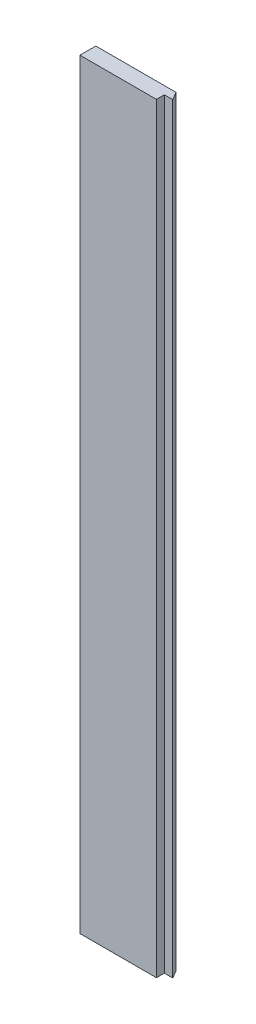
SolidWorks part; units mm, degrees
ref_plane "Front Plane" through (0, 0, 0) normal (0, 0, 1) x (1, 0, 0)
ref_plane "Top Plane" through (0, 0, 0) normal (0, 1, 0) x (1, 0, 0)
ref_plane "Right Plane" through (0, 0, 0) normal (1, 0, 0) x (0, 0, -1)
sketch "Sketch1" plane through (0, 0, 0) normal (0, 1, 0) x (1, 0, 0)
  line L0 (-60, 0) -> (-41.5, 0)
  line L1 (-60, 9) -> (60, 9)
  line L2 (-60, 9) -> (-60, -9)
  line L3 (-60, -9) -> (60, -9)
  line L4 (60, 9) -> (60, -9)
  line L5 (-60, 9) -> (60, -9) construction
  line L6 (-60, -9) -> (60, 9) construction
  line L7 (-41.5, 0) -> (-36.3038, 9)
  line L8 (-41.5, 0) -> (-41.5, 9) construction
  line L9 (60, 0) -> (54.8038, 9)
  line L10 (60, 0) -> (50.5, 0)
  line L11 (50.5, 0) -> (50.5, -9)
  line L13 (0, 9) -> (0, -9) construction
  point P0 (0, 0)
  dimension "D1" = 120
  dimension "D2" = 18
  dimension "D3" = 18.5
  dimension "D4" = 30
  dimension "D5" = 9.5
  dimension "D6" = 30
extrude "Shape" add sketch "Sketch1" along normal blind 1000 contours L3 L11 L10 L9 L1 L7 L0 L2 region at (1.7695, 0, 0.3466)
ref_plane "Plane1" [suppressed] through (-60, 790, 9) normal (0.5851, -0.811, 0) x (-0.811, -0.5851, 0)
sketch "Sketch3" [suppressed] plane through (0, 0, 9) normal (0, 0, 1) x (1, 0, 0)
  line L1 (-60, 790) -> (445, 90) construction
  line L3 (-60, 790) -> (445, 90)
  line L6 (50.5, 0) -> (60, 0)
  line L7 (60, 0) -> (60, 800)
  line L8 (60, 800) -> (50.5, 800)
  line L9 (50.5, 800) -> (50.5, 0)
  line L10 (50.5, 0) -> (60, 0)
  line L11 (60, 0) -> (60, 800)
  line L12 (60, 800) -> (50.5, 800)
  line L13 (50.5, 800) -> (50.5, 0)
  dimension "D1" = 0
extrude "Cut-Extrude1" [suppressed] cut sketch "Sketch3" against normal up to next
sketch "Sketch4" [suppressed] plane through (0, 0, 9) normal (0, 0, 1) x (1, 0, 0)
  line L0 (-170.5, 790) -> (334.5, 90) construction
  line L1 (-170.5, 790) -> (334.5, 90)
  line L6 (50.5, 0) -> (60, 0)
  line L7 (60, 0) -> (60, 800)
  line L8 (60, 800) -> (50.5, 800)
  line L9 (50.5, 800) -> (50.5, 0)
  line L10 (50.5, 0) -> (60, 0)
  line L11 (60, 0) -> (60, 800)
  line L12 (60, 800) -> (50.5, 800)
  line L13 (50.5, 800) -> (50.5, 0)
  dimension "D1" = 0
extrude "Cut-Extrude2" [suppressed] cut sketch "Sketch4" against normal through all and the other way through all
sketch "Sketch5" [suppressed] plane through (0, 0, 9) normal (0, 0, 1) x (1, 0, 0)
  line L0 (-281, 790) -> (224, 90) construction
  line L1 (-281, 790) -> (224, 90)
  line L4 (50.5, 0) -> (60, 0)
  line L5 (60, 0) -> (60, 800)
  line L6 (60, 800) -> (50.5, 800)
  line L7 (50.5, 800) -> (50.5, 0)
  line L8 (50.5, 0) -> (60, 0)
  line L9 (60, 0) -> (60, 800)
  line L10 (60, 800) -> (50.5, 800)
  line L11 (50.5, 800) -> (50.5, 0)
  dimension "D1" = 0
extrude "Cut-Extrude3" [suppressed] cut sketch "Sketch5" against normal up to next
sketch "Sketch6" [suppressed] plane through (0, 0, 9) normal (0, 0, 1) x (1, 0, 0)
  line L0 (-391.5, 790) -> (113.5, 90) construction
  line L1 (-391.5, 790) -> (113.5, 90)
  line L6 (50.5, 0) -> (60, 0)
  line L7 (60, 0) -> (60, 800)
  line L8 (60, 800) -> (50.5, 800)
  line L9 (50.5, 800) -> (50.5, 0)
  line L10 (50.5, 0) -> (60, 0)
  line L11 (60, 0) -> (60, 800)
  line L12 (60, 800) -> (50.5, 800)
  line L13 (50.5, 800) -> (50.5, 0)
  dimension "D1" = 0
extrude "Cut-Extrude4" [suppressed] cut sketch "Sketch6" against normal up to next
sketch "Sketch7" [suppressed] plane through (0, 0, 9) normal (0, 0, 1) x (1, 0, 0)
  line L0 (-502, 790) -> (3, 90) construction
  line L1 (-502, 790) -> (3, 90)
  line L2 (3, 90) -> (3, 0)
  line L3 (-60, 0) -> (50.5, 0) construction
  line L8 (50.5, 0) -> (60, 0)
  line L9 (60, 0) -> (60, 800)
  line L10 (60, 800) -> (50.5, 800)
  line L11 (50.5, 800) -> (50.5, 0)
  line L12 (50.5, 0) -> (60, 0)
  line L13 (60, 0) -> (60, 800)
  line L14 (60, 800) -> (50.5, 800)
  line L15 (50.5, 800) -> (50.5, 0)
  line M5 (-60, 0) -> (50.5, 0)
  line M6 (50.5, 0) -> (50.5, 800)
  line M7 (50.5, 800) -> (-60, 800)
  line M8 (-60, 800) -> (-60, 0)
  dimension "D1" = 0
extrude "Cut-Extrude5" [suppressed] cut sketch "Sketch7" against normal up to next contours L1 L2 M5 M6 M7 M8 | L13 L14 L12 M6
sketch "Sketch8" [suppressed] plane through (0, 0, -9) normal (0, 0, -1) x (-1, 0, 0)
  line L1 (-730.5, 863.1483) -> (129.5, 863.1483) construction
  line L8 (-730.5, 863.1483) -> (129.5, 863.1483)
  line L9 (-50.5, 0) -> (-60, 0) construction
  line L10 (-60, 0) -> (-60, 1000) construction
  line L11 (-60, 1000) -> (-50.5, 1000) construction
  line L12 (-50.5, 1000) -> (-50.5, 0) construction
  line L13 (-54.8038, 0) -> (36.3038, 0) construction
  line L14 (36.3038, 1000) -> (-54.8038, 1000) construction
  line L15 (-54.8038, 1000) -> (-54.8038, 0) construction
  line L16 (36.3038, 0) -> (41.5, 0) construction
  line L17 (41.5, 1000) -> (36.3038, 1000) construction
  line L18 (41.5, 0) -> (60, 0) construction
  line L19 (60, 0) -> (60, 1000) construction
  line L20 (60, 1000) -> (41.5, 1000) construction
  line L21 (-50.5, 0) -> (-60, 0)
  line L22 (-60, 0) -> (-60, 1000)
  line L23 (-60, 1000) -> (-50.5, 1000)
  line L24 (-50.5, 1000) -> (-50.5, 0)
  line L25 (-54.8038, 0) -> (36.3038, 0)
  line L26 (36.3038, 1000) -> (-54.8038, 1000)
  line L27 (-54.8038, 1000) -> (-54.8038, 0)
  line L28 (36.3038, 0) -> (41.5, 0)
  line L29 (41.5, 1000) -> (36.3038, 1000)
  line L30 (41.5, 0) -> (60, 0)
  line L31 (60, 0) -> (60, 1000)
  line L32 (60, 1000) -> (41.5, 1000)
extrude "Cut-Extrude6" [suppressed] cut sketch "Sketch8" against normal up to next
sketch "Sketch9" [suppressed] plane through (0, 0, -9) normal (0, 0, -1) x (-1, 0, 0)
  line L0 (-60, 1000) -> (-60, 0) construction
  line L1 (60, 1000) -> (-60, 1000)
  line L2 (60, 1000) -> (60, 863.1483)
  line L3 (60, 863.1483) -> (-60, 863.1483)
  line L4 (-60, 1000) -> (-60, 863.1483)
  line L5 (-841, 863.1483) -> (19, 863.1483) construction
  point P9 (0, 863.1483)
extrude "Cut-Extrude7" [suppressed] cut sketch "Sketch9" against normal up to next
sketch "Sketch10" plane through (0, 0, -9) normal (0, 0, -1) x (-1, 0, 0)
  line L0 (36.3038, 0) -> (-54.8038, 0) construction
  line L1 (36.3038, 1000) -> (60, 1000)
  line L2 (36.3038, 1000) -> (36.3038, 0)
  line L3 (36.3038, 0) -> (60, 0)
  line L4 (60, 1000) -> (60, 0)
  line L5 (60, 1000) -> (60, 0) construction
  line L7 (-60, 1000) -> (-60, 0) construction
  line L8 (60, 1000) -> (-60, 1000)
  line L9 (60, 1000) -> (60, 863.1483)
  line L10 (60, 863.1483) -> (-60, 863.1483)
  line L11 (-60, 1000) -> (-60, 863.1483)
  line L12 (537.107, 863.1483) -> (-71.0048, 863.1483) construction
  line M4 (36.3038, 0) -> (36.3038, 1000)
  line M5 (36.3038, 1000) -> (-54.8038, 1000)
  line M6 (-54.8038, 1000) -> (-54.8038, 0)
extrude "Cut-Extrude8" cut sketch "Sketch10" against normal up to next contours L8 L11 L10 M6 | L10 L2 M5 M6 | L10 L4 L1 L2 | L4 L10 L3 M4 region at (-48.1519, 931.5742, -9) region at (9.25, 931.5742, -9) region at (-48.1519, 431.5742, -9) region at (57.4019, 931.5742, -9)
